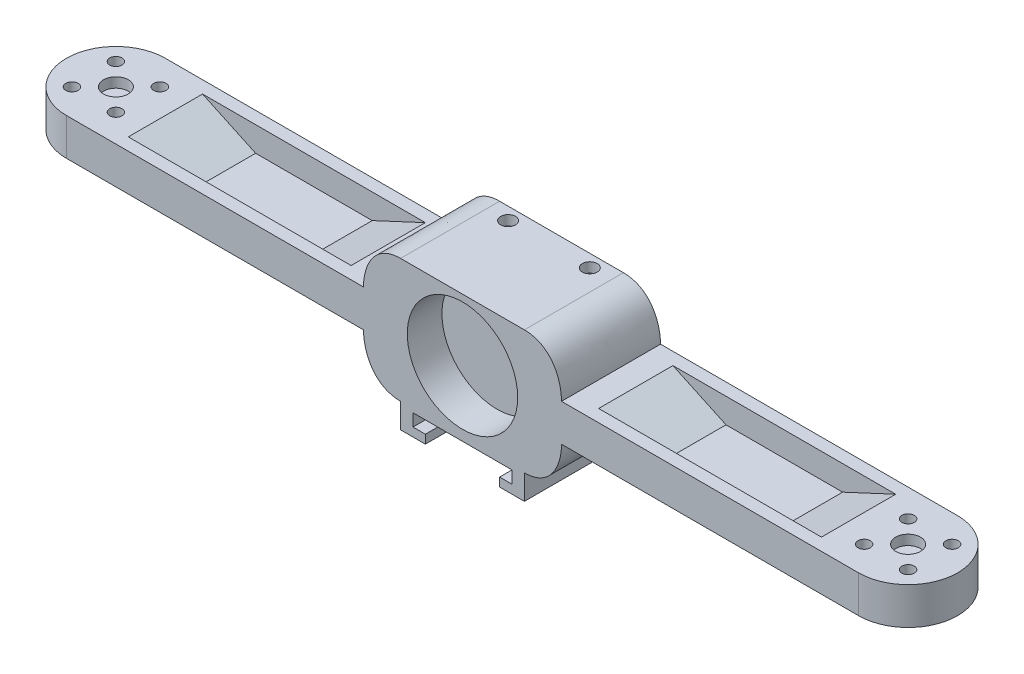
SolidWorks part; units mm, degrees
ref_plane "Front Plane" through (0, 0, 0) normal (0, 0, 1) x (1, 0, 0)
ref_plane "Top Plane" through (0, 0, 0) normal (0, 1, 0) x (1, 0, 0)
ref_plane "Right Plane" through (0, 0, 0) normal (1, 0, 0) x (0, 0, -1)
sketch "Sketch1" plane through (0, 0, 0) normal (0, 1, 0) x (1, 0, 0)
  line L0 (-80, 0) -> (80, 0) construction
  line L1 (-80, 10) -> (80, 10)
  line L2 (-80, -10) -> (80, -10)
  arc A0 (-80, 10) -> (-80, -10) centre (-80, 0) ccw
  arc A1 (80, -10) -> (80, 10) centre (80, 0) ccw
  point P2 (0, 0)
  dimension "D1" = 160
  dimension "D2" = 20
extrude "Boss-Extrude1" add sketch "Sketch1" along normal blind 25 contours L1 A1 L2 A0
sketch "Sketch2" plane through (0, 0, 10) normal (0, 0, 1) x (1, 0, 0)
  line L0 (0, 0) -> (0, 12.5) construction
  circle A0 centre (0, 12.5) radius 11.15
  dimension "D2" = 22.3
  dimension "D1" = 12.5
extrude "Cut-Extrude1" cut sketch "Sketch2" against normal blind 7 contours A0
sketch "Sketch3" plane through (0, 25, 0) normal (0, 1, 0) x (1, 0, 0)
  line L0 (0, 0) -> (20, 0) construction
  line L1 (0, 0) -> (-20, 0) construction
  line L2 (-20, 10) -> (-20, -10)
  line L3 (-80, 10) -> (80, 10) construction
  line L4 (-80, -10) -> (80, -10) construction
  line L5 (20, 10) -> (20, -10)
  line L6 (20, -10) -> (80, -10)
  line L7 (20, 10) -> (80, 10)
  line L8 (-20, 10) -> (-80, 10)
  line L9 (-20, -10) -> (-80, -10)
  arc A0 (-80, 10) -> (-80, -10) centre (-80, 0) ccw
  arc A1 (80, 10) -> (80, -10) centre (80, 0) cw
  dimension "D2" = 20
  dimension "D1" = 20
extrude "Cut-Extrude2" cut sketch "Sketch3" against normal blind 8.75
sketch "Sketch4" plane through (0, 0, 0) normal (0, -1, 0) x (1, 0, 0)
  line L2 (20, 10) -> (20, -10)
  line L3 (-80, 10) -> (80, 10) construction
  line L4 (20, -10) -> (80, -10)
  line L5 (20, 10) -> (80, 10)
  line L6 (-20, 10) -> (-20, -10)
  line L7 (-20, -10) -> (-80, -10)
  line L8 (-20, 10) -> (-80, 10)
  arc A0 (80, 10) -> (80, -10) centre (80, 0) cw
  arc A1 (-80, 10) -> (-80, -10) centre (-80, 0) ccw
extrude "Cut-Extrude3" cut sketch "Sketch4" against normal blind 8.75
sketch "Sketch5" plane through (0, 0, -10) normal (0, 0, -1) x (-1, 0, 0)
  line L0 (0, 0) -> (0, 12.5) construction
  line L2 (-12.5, 2.25) -> (12.5, 2.25)
  line L3 (-12.5, 2.25) -> (-12.5, 22.75)
  line L4 (-12.5, 22.75) -> (12.5, 22.75)
  line L5 (12.5, 2.25) -> (12.5, 22.75)
  line L6 (-12.5, 2.25) -> (12.5, 22.75) construction
  line L7 (-12.5, 22.75) -> (12.5, 2.25) construction
  dimension "D1" = 12.5
  dimension "D2" = 25
  dimension "D3" = 20.5
extrude "Cut-Extrude4" cut sketch "Sketch5" against normal blind 8
sketch "Sketch9" plane through (0, 16.25, 0) normal (0, 1, 0) x (1, 0, 0)
  line L0 (-80, 10) -> (-80, -10) construction
  line L1 (0, 0) -> (0, 5) construction
  circle A0 centre (-80, 0) radius 2.5
  circle A1 centre (80, 0) radius 2.5
  dimension "D1" = 5
  dimension "D2" = 5
extrude "Cut-Extrude5" cut sketch "Sketch9" against normal blind 2
sketch "Sketch10" plane through (0, 16.25, 0) normal (0, 1, 0) x (1, 0, 0)
  line L0 (-80, 0) -> (-80, 4.44) construction
  line L1 (-80, 4.44) -> (-75.56, 4.44) construction
  line L2 (0, 0) -> (0, 5) construction
  circle A0 centre (-75.56, 4.44) radius 1.25
  circle A1 centre (-75.56, -4.44) radius 1.25
  circle A2 centre (-84.44, -4.44) radius 1.25
  circle A3 centre (-84.44, 4.44) radius 1.25
  circle A4 centre (84.44, 4.44) radius 1.25
  circle A5 centre (84.44, -4.44) radius 1.25
  circle A6 centre (75.56, -4.44) radius 1.25
  circle A7 centre (75.56, 4.44) radius 1.25
  point P14 (-80, 0)
  dimension "D3" = 2.5
  dimension "D1" = 4.44
  dimension "D2" = 4.44
  dimension "D5" = 5
  dimension "D4" = 4
extrude "Cut-Extrude6" cut sketch "Sketch10" against normal up to next
sketch "Sketch13" plane through (0, 8.75, 0) normal (0, -1, 0) x (1, 0, 0)
  line L0 (-80, 10) -> (-80, -10) construction
  line L1 (-80, 0) -> (-75.56, 0) construction
  line L2 (-75.56, 0) -> (-75.56, 4.44) construction
  line L3 (0, 0) -> (0, 5) construction
  circle A0 centre (-75.56, 4.44) radius 2.4
  circle A1 centre (-75.56, -4.44) radius 2.4
  circle A2 centre (-84.44, -4.44) radius 2.4
  circle A3 centre (-84.44, 4.44) radius 2.4
  circle A4 centre (84.44, 4.44) radius 2.4
  circle A5 centre (84.44, -4.44) radius 2.4
  circle A6 centre (75.56, -4.44) radius 2.4
  circle A7 centre (75.56, 4.44) radius 2.4
  point P18 (-80, 0)
  dimension "D1" = 4.44
  dimension "D2" = 4.44
  dimension "D5" = 5
  dimension "D4" = 4
  dimension "D3" = 4.8
extrude "Cut-Extrude7" cut sketch "Sketch13" against normal offset from surface (4.5 mm away) 3 up to face at (84.44, 16.25, -5.69)
sketch "Sketch14" plane through (0, 25, 0) normal (0, 1, 0) x (1, 0, 0)
  line L0 (0, 0) -> (0, 10) construction
  line L1 (-20, 10) -> (20, 10) construction
  line L2 (0, 10) -> (-8.25, 10) construction
  line L3 (-8.25, 10) -> (-8.25, 7.46) construction
  circle A0 centre (-8.25, 7.46) radius 1.5
  circle A1 centre (8.25, 7.46) radius 1.5
  dimension "D3" = 3
  dimension "D1" = 8.25
  dimension "D2" = 2.54
extrude "Cut-Extrude8" cut sketch "Sketch14" against normal blind 2
sketch "Sketch16" plane through (0, 0, -10) normal (0, 0, -1) x (-1, 0, 0)
  line L0 (0, 0) -> (0, 25) construction
  line L1 (20, 25) -> (-20, 25) construction
  line L2 (-12.5, 22.75) -> (-12.5, 25) construction
  line L3 (0, 12.5) -> (-20, 12.5) construction
  line L4 (-12.5, 25) -> (-20, 25)
  line L5 (-20, 25) -> (-20, 16.25)
  line L6 (12.5, 25) -> (20, 25)
  line L7 (20, 25) -> (20, 16.25)
  line L8 (20, 0) -> (20, 8.75)
  line L9 (12.5, 0) -> (20, 0)
  line L10 (-20, 0) -> (-20, 8.75)
  line L11 (-12.5, 0) -> (-20, 0)
  spline S0 degree 3 poles (-20, 16.25) (-20, 20.0915) (-17.8821, 25) (-12.5, 25) knots 0 0 0 0 1 1 1 1
  spline S1 degree 3 poles (20, 16.25) (20, 20.0915) (17.8821, 25) (12.5, 25) knots 0 0 0 0 1 1 1 1
  spline S2 degree 3 poles (20, 8.75) (20, 4.9085) (17.8821, 0) (12.5, 0) knots 0 0 0 0 1 1 1 1
  spline S3 degree 3 poles (-20, 8.75) (-20, 4.9085) (-17.8821, 0) (-12.5, 0) knots 0 0 0 0 1 1 1 1
  dimension "D2" = 20
extrude "Cut-Extrude10" cut sketch "Sketch16" against normal blind 20
sketch "Sketch17" plane through (0, 0, -10) normal (0, 0, -1) x (-1, 0, 0)
  line L0 (12.5, 0) -> (12.5, -5)
  line L1 (-12.5, 0) -> (12.5, 0)
  line L5 (12.5, -5) -> (7.5, -5)
  line L17 (7.5, -5) -> (7.5, -3.25)
  line L18 (7.5, -3.25) -> (10, -3.25)
  line L19 (10, -3.25) -> (10, -0.75)
  line L20 (10, -0.75) -> (-10, -0.75)
  line L21 (-10, -0.75) -> (-10, -3.25)
  line L22 (-10, -3.25) -> (-7.5, -3.25)
  line L23 (-7.5, -3.25) -> (-7.5, -5)
  line L24 (-7.5, -5) -> (-12.5, -5)
  line L25 (-12.5, -5) -> (-12.5, 0)
  dimension "D1" = 20
  dimension "D2" = 25
  dimension "D3" = 2.5
  dimension "D4" = 2.5
  dimension "D5" = 5
  dimension "D6" = 2.5
  dimension "D7" = 1.75
  dimension "D8" = 1.75
  dimension "D9" = 2.5
  dimension "D10" = 5
extrude "Boss-Extrude2" add sketch "Sketch17" against normal blind 20
sketch "Sketch18" plane through (0, 16.25, 0) normal (0, 1, 0) x (1, 0, 0)
  line L0 (0, 0) -> (-20, 0) construction
  line L1 (-20, -10) -> (-20, 10) construction
  line L2 (-90, 0) -> (-70, 0) construction
  line L3 (-20, 0) -> (-25, 0) construction
  line L4 (-70, 0) -> (-25, 0) construction
  line L5 (-20, 10) -> (-25, 10) construction
  line L6 (-20, 10) -> (-80, 10) construction
  line L7 (-25, 10) -> (-25, 7.5) construction
  line L8 (0, 0) -> (0, 10) construction
  line L9 (70, 7.5) -> (25, 7.5)
  line L10 (-70, -7.5) -> (-25, -7.5)
  line L11 (-70, -7.5) -> (-70, 7.5)
  line L12 (-70, 7.5) -> (-25, 7.5)
  line L13 (-25, -7.5) -> (-25, 7.5)
  line L14 (-70, -7.5) -> (-25, 7.5) construction
  line L15 (-70, 7.5) -> (-25, -7.5) construction
  line L16 (25, -7.5) -> (25, 7.5)
  line L17 (70, -7.5) -> (25, -7.5)
  line L18 (70, -7.5) -> (70, 7.5)
  line L19 (70, 7.5) -> (25, -7.5) construction
  line L20 (70, -7.5) -> (25, 7.5) construction
  arc A0 (-80, 10) -> (-80, -10) centre (-80, 0) ccw construction
  point P17 (-47.5, 0)
  point P27 (47.5, 0)
  dimension "D1" = 20
  dimension "D2" = 5
  dimension "D3" = 5
  dimension "D4" = 2.5
  dimension "D5" = 10
extrude "Cut-Extrude11" cut sketch "Sketch18" against normal blind 5
sketch "Sketch20" plane through (0, 0, 10) normal (0, 0, 1) x (1, 0, 0)
  line L0 (-25, 11.25) -> (-25, 16.25)
  line L4 (-25, 11.25) -> (-35.7225, 11.25)
  line L5 (-70, 11.25) -> (-25, 11.25) construction
  line L6 (-35.7225, 11.25) -> (-25, 16.25)
  line L7 (-47.5, 11.25) -> (-47.5, 16.25) construction
  line L8 (-80, 16.25) -> (-20, 16.25) construction
  line L9 (-70, 11.25) -> (-59.2775, 11.25)
  line L10 (-70, 11.25) -> (-70, 16.25)
  line L11 (-59.2775, 11.25) -> (-70, 16.25)
  line L12 (0, 0) -> (0, 25) construction
  line L13 (-12.5, 25) -> (12.5, 25) construction
  line L14 (25, 11.25) -> (35.7225, 11.25)
  line L15 (25, 11.25) -> (25, 16.25)
  line L16 (35.7225, 11.25) -> (25, 16.25)
  line L17 (70, 11.25) -> (70, 16.25)
  line L18 (59.2775, 11.25) -> (70, 16.25)
  line L19 (70, 11.25) -> (59.2775, 11.25)
  dimension "D1" = 65
extrude "Boss-Extrude3" add sketch "Sketch20" against normal blind 20
equation "\"Cent to Cent length\"= 16cm"
equation "\"D1@Sketch1\"=\"Cent to Cent length\""
equation "\"Width\"= 2cm"
equation "\"D2@Sketch1\"=\"Width\""
equation "\"XY for Motor Mounts\"= .444cm"
equation "\"Diam for large MM hole\"= .48cm"
equation "\"Diam for small MM hole\"= .25cm"
equation "\"D1@Sketch10\"=\"XY for Motor Mounts\""
equation "\"D2@Sketch10\"=\"XY for Motor Mounts\""
equation "\"D3@Sketch10\"=\"Diam for small MM hole\""
equation "\"D1@Sketch13\"=\"XY for Motor Mounts\""
equation "\"D2@Sketch13\"=\"XY for Motor Mounts\""
equation "\"D3@Sketch13\"=\"Diam for large MM hole\""
equation "\"Hole distance / 2 for Accelerometer\"= 8.25mm"
equation "\"Hole distance from edge for accelerometer\"= 2.54mm"
equation "\"D1@Sketch14\"=\"Hole distance / 2 for Accelerometer\""
equation "\"D2@Sketch14\"=\"Hole distance from edge for accelerometer\""
equation "\"Center Housing Width/2\"= 2cm"
equation "\"D1@Sketch3\"=\"Center Housing Width/2\""
equation "\"D2@Sketch3\"=\"Center Housing Width/2\""
equation "\"D2@Sketch16\"=\"Center Housing Width/2\""
equation "\"D1@Cut-Extrude10\"=\"Width\""
equation "\"D1@Boss-Extrude2\"=\"Width\""
equation "\"D1@Boss-Extrude3\"=\"Width\""
equation "\"Draft Angle, ESC Recess\"= 65deg"
equation "\"D1@Sketch20\"=\"Draft Angle, ESC Recess\""
equation "\"Screw Depth for Motors\"= .3cm"
equation "\"D1@Cut-Extrude7\"=\"Screw Depth for Motors\""
